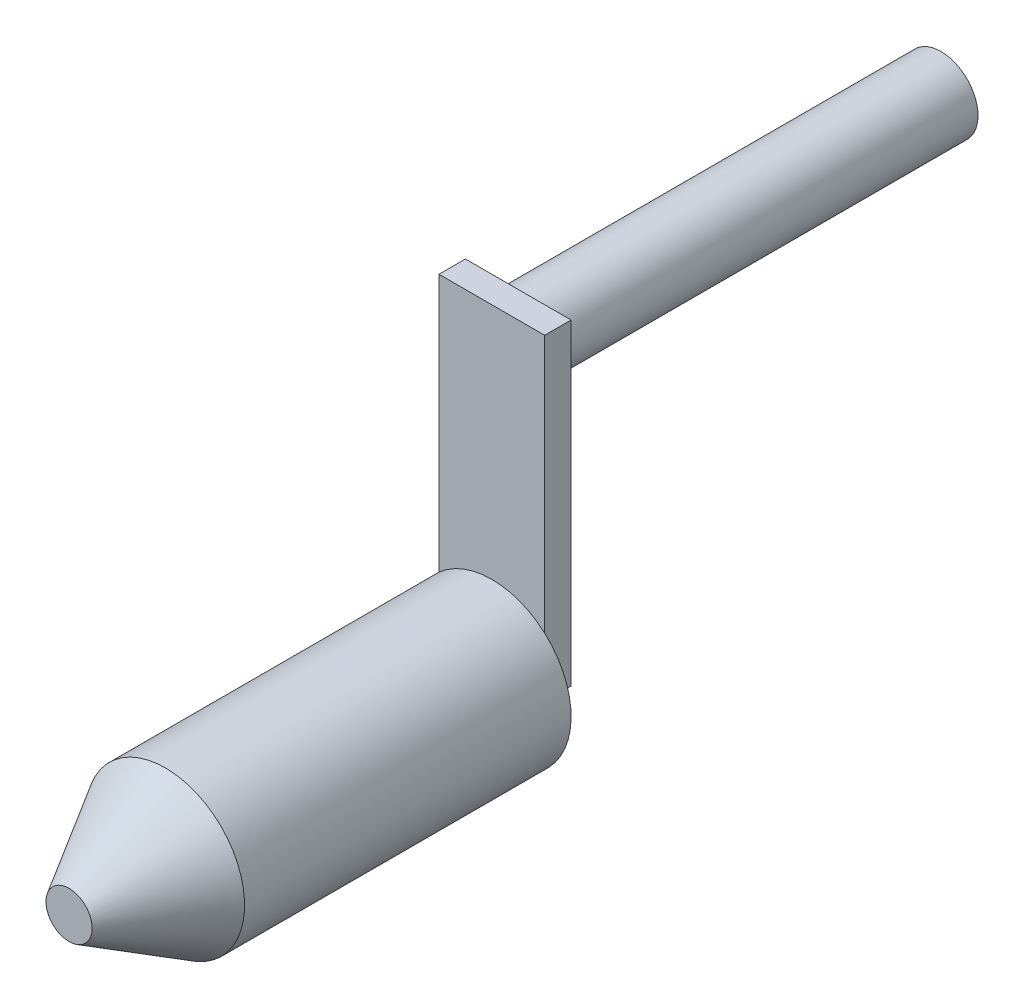
SolidWorks part; units mm, degrees
ref_plane "Front Plane" through (0, 0, 0) normal (0, 0, 1) x (1, 0, 0)
ref_plane "Top Plane" through (0, 0, 0) normal (0, 1, 0) x (1, 0, 0)
ref_plane "Right Plane" through (0, 0, 0) normal (1, 0, 0) x (0, 0, -1)
sketch "Sketch1" plane through (0, 0, 0) normal (0, 0, 1) x (1, 0, 0)
  circle A0 centre (0, 0) radius 9.525
  dimension "D1" = 19.05
extrude "Boss-Extrude1" add sketch "Sketch1" along normal blind 50.8
sketch "Sketch2" plane through (0, 0, 0) normal (0, 0, -1) x (-1, 0, 0)
  line L1 (-6.35, 0) -> (6.35, 0)
  line L2 (-6.35, 0) -> (-6.35, 38.1)
  line L3 (-6.35, 38.1) -> (6.35, 38.1)
  line L4 (6.35, 0) -> (6.35, 38.1)
  point P0 (0, 0)
  point P6 (5.0069, 16.0776)
  point P7 (0, 0)
  dimension "D1" = 12.7
  dimension "D2" = 38.1
extrude "Boss-Extrude2" add sketch "Sketch2" along normal blind 3.175
sketch "Sketch3" plane through (0, 0, -3.175) normal (0, 0, -1) x (-1, 0, 0)
  line L0 (0, 33.02) -> (0, 0) construction
  circle A0 centre (0, 33.02) radius 4.445
  dimension "D1" = 8.89
  dimension "D2" = 33.02
extrude "Boss-Extrude3" add sketch "Sketch3" along normal blind 50.8
sketch "Sketch4" plane through (0, 0, 0) normal (1, 0, 0) x (0, 0, -1)
  line L0 (-50.8, 2.7713) -> (-39.2321, 9.525)
  line L1 (-50.8, 9.525) -> (-50.8, -9.525) construction
  line L2 (-39.2321, 9.525) -> (-50.8, 9.525)
  line L3 (-50.8, 9.525) -> (-50.8, 2.7713)
  line L4 (0.7894, 0) -> (-54.9671, 0) construction
revolve "Cut-Revolve1" cut sketch "Sketch4" angle 360 about L4
ref_point "Point1"
ref_axis "Axis1" through (0, 0, 39.2321) along (0, 0, -1)
